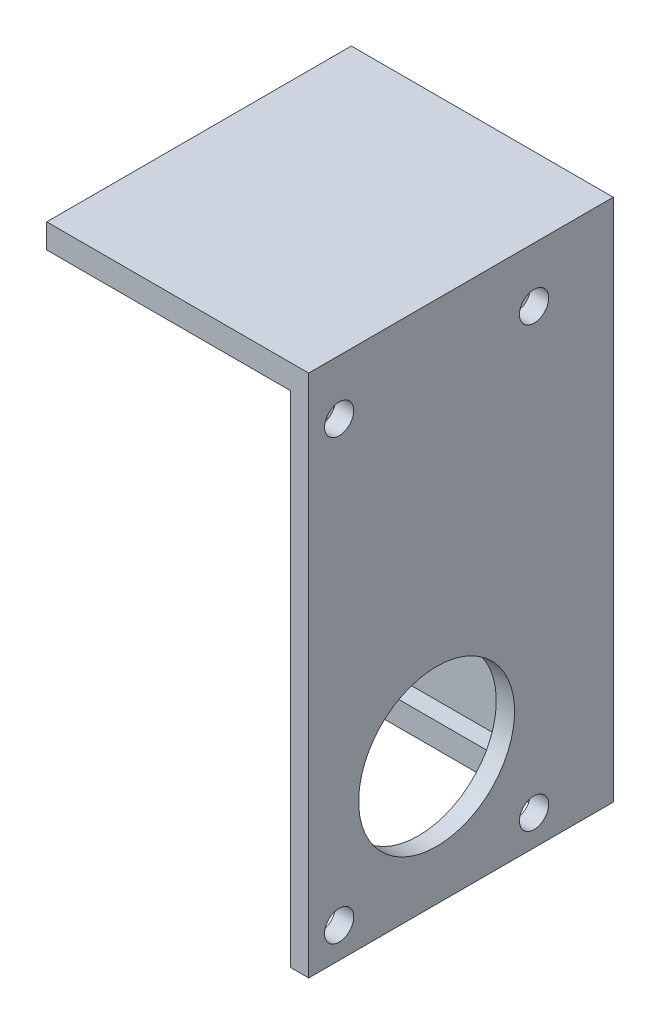
SolidWorks part; units mm, degrees
ref_plane "前基準面" through (0, 0, 0) normal (0, 0, 1) x (1, 0, 0)
ref_plane "上基準面" through (0, 0, 0) normal (0, 1, 0) x (1, 0, 0)
ref_plane "右基準面" through (0, 0, 0) normal (1, 0, 0) x (0, 0, -1)
sketch "草圖1" plane through (0, 0, 0) normal (0, 0, 1) x (1, 0, 0)
  line L0 (0, 20.5) -> (0, -20.5) construction
  line L1 (-10, 20.5) -> (10, 20.5)
  line L2 (-10, 20.5) -> (-10, -20.5)
  line L3 (-10, -20.5) -> (10, -20.5)
  line L4 (10, 20.5) -> (10, -20.5)
  line L5 (-10, 20.5) -> (10, -20.5) construction
  line L6 (-10, -20.5) -> (10, 20.5) construction
  line L7 (10, 20.5) -> (11.5, 20.5)
  line L8 (10, 20.5) -> (10, -20.5)
  line L9 (10, -20.5) -> (11.5, -20.5)
  line L10 (11.5, 20.5) -> (11.5, -20.5)
  line L16 (11.5, 20.5) -> (-10, 20.5)
  line L17 (11.5, 20.5) -> (11.5, 22.5)
  line L18 (11.5, 22.5) -> (-10, 22.5)
  line L19 (-10, 20.5) -> (-10, 22.5)
  circle A0 centre (0, 7) radius 1.3
  circle A1 centre (4.9497, 4.9497) radius 1.3
  circle A2 centre (7, 0) radius 1.3
  circle A3 centre (4.9497, -4.9497) radius 1.3
  circle A4 centre (0, -7) radius 1.3
  circle A5 centre (-4.9497, -4.9497) radius 1.3
  circle A6 centre (-7, 0) radius 1.3
  circle A7 centre (-4.9497, 4.9497) radius 1.3
  point P0 (0, 0)
  point P28 (0, 0)
  dimension "D4" = 2.6
  dimension "D1" = 20
  dimension "D2" = 1.5
  dimension "D3" = 41
  dimension "D5" = 7
  dimension "D7" = 2
  dimension "D6" = 8
extrude "填料-伸長1" add sketch "草圖1" along normal blind 2 contours L4 L1 L2 L3 A7 A6 A5 A4 A3 A2 A1 A0 region at (0, 0, 0)
extrude "填料-伸長2" add sketch "草圖1<3>" along normal blind 25 contours L10 L7 L4 L9 region at (10.75, 0, 0)
sketch "草圖1<3>" plane through (0, 0, 0) normal (0, 0, 1) x (1, 0, 0) same geometry as "草圖1"
sketch "草圖2" plane through (11.5, 0, 0) normal (1, 0, 0) x (0, 0, -1)
  line L0 (-25, 20.5) -> (0, 20.5) construction
  line L4 (-25, -20.5) -> (-4, -20.5)
  line L5 (-25, -20.5) -> (-25, 20.5)
  line L6 (-25, 20.5) -> (-4, 20.5)
  line L7 (-4, -20.5) -> (-4, 20.5)
  line L8 (-14.5, -20.5) -> (-14.5, 20.5) construction
  line L9 (-25, 0) -> (-4, 0) construction
  circle A1 centre (-22.5, -18) radius 1.2
  circle A2 centre (-22.5, 18) radius 1.2
  circle A3 centre (-6.5, 18) radius 1.2
  circle A4 centre (-6.5, -18) radius 1.2
  circle A5 centre (-14.5, -10) radius 6.4
  dimension "D4" = 2.4
  dimension "D5" = 12.8
  dimension "D1" = 21
  dimension "D2" = 18
  dimension "D3" = 8
  dimension "D6" = 10
extrude "除料-伸長1" cut sketch "草圖2" against normal through all contours A1 | A4 | A2 | A3 | A5 region at (11.5, -18, 22.5) region at (11.5, 18, 22.5) region at (11.5, 18, 6.5) region at (11.5, -18, 6.5) region at (11.5, -10, 14.5)
extrude "填料-伸長6" add sketch "草圖1<6>" along normal blind 25 contours L19 L1 L7 L17 L18 region at (0.75, 21.5, 0)
sketch "草圖1<6>" plane through (0, 0, 0) normal (0, 0, 1) x (1, 0, 0) same geometry as "草圖1"
sketch "草圖4" plane through (0, 0, 2) normal (0, 0, 1) x (1, 0, 0)
  line L0 (-10, 20.5) -> (-10, -20.5) construction
  line L1 (10, -20.5) -> (-10, -20.5)
  line L2 (10, -20.5) -> (10, -18.5)
  line L3 (10, -18.5) -> (-10, -18.5)
  line L4 (-10, -20.5) -> (-10, -18.5)
  dimension "D1" = 2
extrude "填料-伸長8" add sketch "草圖4" along normal blind 1.5
mirror "鏡射1" about plane through (0, 0, 0) normal (0, 1, 0) of "填料-伸長8"
